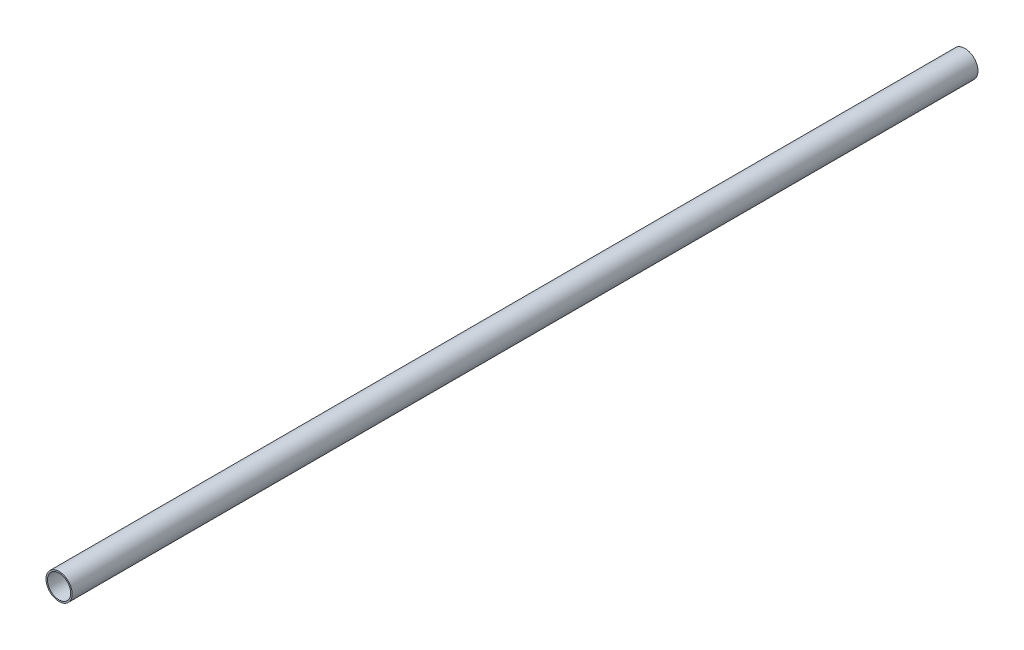
SolidWorks part; units mm, degrees
material "6061-T6 (SS)"
ref_plane "Front Plane" through (0, 0, 0) normal (0, 0, 1) x (1, 0, 0)
ref_plane "Top Plane" through (0, 0, 0) normal (0, 1, 0) x (1, 0, 0)
ref_plane "Right Plane" through (0, 0, 0) normal (1, 0, 0) x (0, 0, -1)
sketch "Sketch1" plane through (0, 0, 0) normal (0, 0, 1) x (1, 0, 0)
  circle A0 centre (0, 0) radius 3.175
  circle A1 centre (0, 0) radius 3.575
  dimension "D1" = 6.35
  dimension "D2" = 7.1501
extrude "Boss-Extrude1" add sketch "Sketch1" along normal mid plane 247.65
